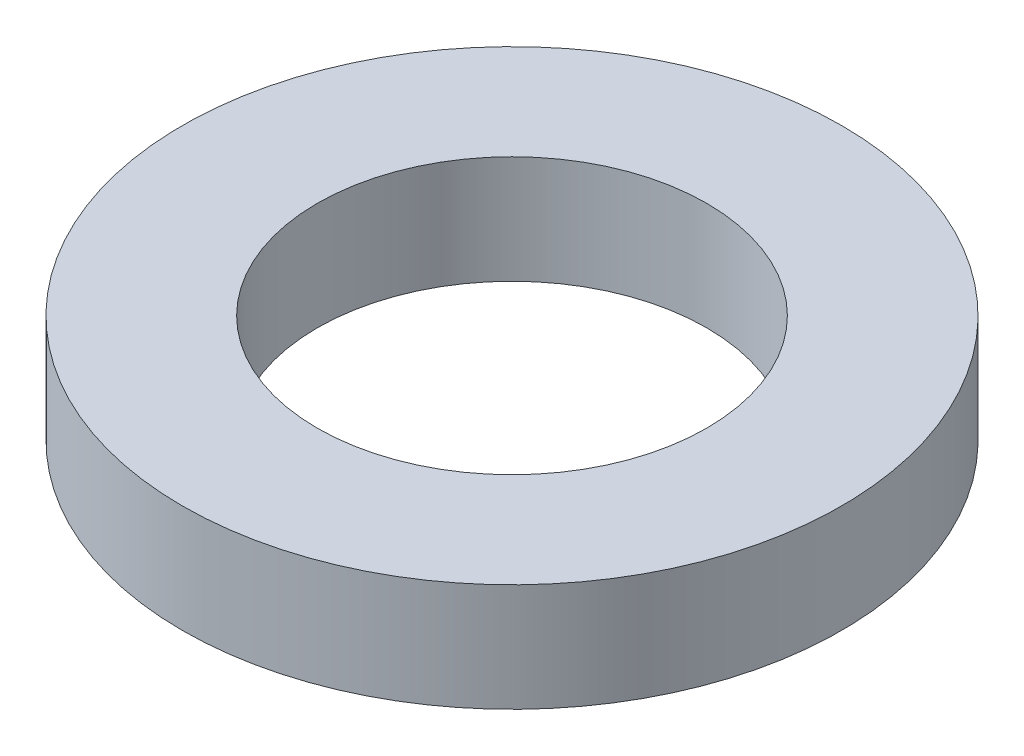
SolidWorks part; units mm, degrees
ref_plane "Front Plane" through (0, 0, 0) normal (0, 0, 1) x (1, 0, 0)
ref_plane "Top Plane" through (0, 0, 0) normal (0, 1, 0) x (1, 0, 0)
ref_plane "Right Plane" through (0, 0, 0) normal (1, 0, 0) x (0, 0, -1)
sketch "Sketch1" plane through (0, 0, 0) normal (0, 1, 0) x (1, 0, 0)
  circle A0 centre (0, 0) radius 55
  dimension "FLANGE_OD" = 110
extrude "Boss-Extrude1" add sketch "Sketch1" along normal blind 18
sketch "Sketch2" plane through (0, 0, 0) normal (0, 1, 0) x (1, 0, 0)
  circle A0 centre (0, 0) radius 32.5
  dimension "BORE_D" = 65
extrude "Cut-Extrude1" cut sketch "Sketch2" along normal through all
sketch "Sketch3" plane through (0, 18, 0) normal (0, 1, 0) x (1, 0, 0)
  circle A0 centre (0, 0) radius 19.6062 construction
  circle A1 centre (-19.6062, 0) radius 3.1747
  dimension "BOLT_D" = 6.3493
  dimension "BOLT_PCD" = 39.2125
extrude "Cut-Extrude2" cut sketch "Sketch3" against normal blind 15.7448 rebuild error yes
pattern_circular "CirPattern1" count 8 over 360 rebuild error yes
